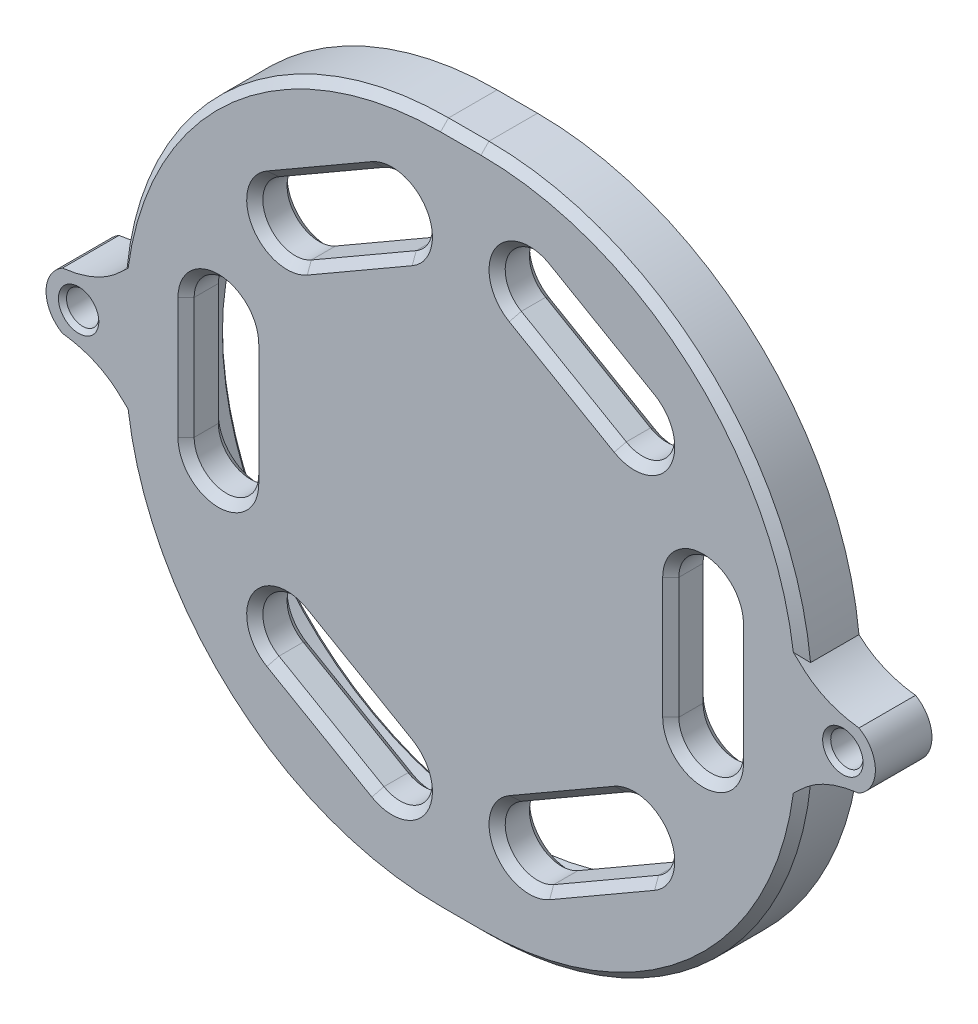
SolidWorks part; units mm, degrees
ref_plane "Plan de face" through (0, 0, 0) normal (0, 0, 1) x (1, 0, 0)
ref_plane "Plan de dessus" through (0, 0, 0) normal (0, 1, 0) x (1, 0, 0)
ref_plane "Plan de droite" through (0, 0, 0) normal (1, 0, 0) x (0, 0, -1)
sketch "Esquisse1" plane through (0, 0, 0) normal (0, 0, 1) x (1, 0, 0)
  line L1 (-2.5, -42.5) -> (2.5, -42.5)
  line L2 (-42.5, -2.5) -> (-42.5, 2.5)
  line L3 (-2.5, 42.5) -> (2.5, 42.5)
  line L4 (42.5, -2.5) -> (42.5, 2.5)
  line L5 (-42.5, -42.5) -> (42.5, 42.5) construction
  line L6 (-42.5, 42.5) -> (42.5, -42.5) construction
  arc A0 (-2.5, -42.5) -> (-42.5, -2.5) centre (-2.5, -2.5) cw
  arc A1 (2.5, 42.5) -> (42.5, 2.5) centre (2.5, 2.5) cw
  arc A2 (2.5, -42.5) -> (42.5, -2.5) centre (2.5, -2.5) ccw
  arc A3 (-42.5, 2.5) -> (-2.5, 42.5) centre (-2.5, 2.5) cw
  point P0 (0, 0)
  dimension "D3" = 40
  dimension "D1" = 85
  dimension "D2" = 85
extrude "Boss.-Extru.1" add sketch "Esquisse1" along normal blind 7
sketch "Esquisse2" plane through (0, 0, 0) normal (0, 0, -1) x (-1, 0, 0)
  circle A0 centre (0, 0) radius 36
  dimension "D1" = 72
extrude "Enlèv. mat.-Extru.1" cut sketch "Esquisse2" against normal blind 2
sketch "Esquisse3" plane through (0, 0, 0) normal (0, 0, -1) x (-1, 0, 0)
  line L0 (0, 0) -> (0, 9.4107) construction
  line L5 (-42.2995, 6.5) -> (-42.2995, -6.5)
  line L6 (-49.2995, 3.5) -> (-49.2995, -3.5) construction
  line L7 (42.2995, 6.5) -> (42.2995, -6.5)
  arc A0 (-49.2995, 3.5) -> (-49.2995, -3.5) centre (-47.2995, 0) ccw
  arc A1 (-2.5, 42.5) -> (-42.5, 2.5) centre (-2.5, 2.5) ccw construction
  arc A2 (-42.5, -2.5) -> (-2.5, -42.5) centre (-2.5, -2.5) ccw construction
  circle A3 centre (-47.2995, 0) radius 2
  circle A4 centre (47.2995, 0) radius 2
  arc A5 (49.2995, 3.5) -> (49.2995, -3.5) centre (47.2995, 0) cw
  spline S0 degree 2 poles (-49.2995, 3.5) (-45, 4) (-42.2995, 6.5) knots 0 0 0 0.627422 0.627422 0.627422
  spline S1 degree 2 poles (-49.2995, -3.5) (-45, -4) (-42.2995, -6.5) knots 0 0 0 0.742649 0.742649 0.742649
  spline S2 degree 2 poles (49.2995, 3.5) (45, 4) (42.2995, 6.5) knots 0 0 0 0.627422 0.627422 0.627422
  spline S3 degree 2 poles (49.2995, -3.5) (45, -4) (42.2995, -6.5) knots 0 0 0 0.742649 0.742649 0.742649
  dimension "D3" = 4
  dimension "D1" = 7
  dimension "D2" = 13
  dimension "D4" = 5
  dimension "D5" = 7
extrude "Boss.-Extru.2" add sketch "Esquisse3" against normal blind 7
chamfer "Chanfrein1" distance 0.5 angle 45 2 edges at (-45.2995, 0, 7) (45.2995, 0, 7)
chamfer "Chanfrein3" distance 0.5 angle 45 1 edges at (-36, 0, 0)
sketch "Esquisse4" plane through (0, 0, 7) normal (0, 0, 1) x (1, 0, 0)
  line L0 (10, 0) -> (30, 0) construction
  line L1 (30, -7.5) -> (30, 7.5)
  line L7 (30, 7.5) -> (30, -7.5) construction
  line L8 (34, 7.5) -> (34, -7.5)
  line L9 (26, 7.5) -> (26, -7.5)
  line L10 (19.4952, -18.7667) -> (6.5048, -26.2667)
  line L11 (23.4952, -25.6949) -> (10.5048, -33.1949)
  line L12 (21.4952, -22.2308) -> (8.5048, -29.7308) construction
  line L13 (-6.5048, -26.2667) -> (-19.4952, -18.7667)
  line L14 (-10.5048, -33.1949) -> (-23.4952, -25.6949)
  line L15 (-8.5048, -29.7308) -> (-21.4952, -22.2308) construction
  line L16 (-26, -7.5) -> (-26, 7.5)
  line L17 (-34, -7.5) -> (-34, 7.5)
  line L18 (-30, -7.5) -> (-30, 7.5) construction
  line L19 (-19.4952, 18.7667) -> (-6.5048, 26.2667)
  line L20 (-23.4952, 25.6949) -> (-10.5048, 33.1949)
  line L21 (-21.4952, 22.2308) -> (-8.5048, 29.7308) construction
  line L22 (6.5048, 26.2667) -> (19.4952, 18.7667)
  line L23 (10.5048, 33.1949) -> (23.4952, 25.6949)
  line L24 (8.5048, 29.7308) -> (21.4952, 22.2308) construction
  line L25 (0, 0) -> (10, 0) construction
  arc A0 (34, 7.5) -> (26, 7.5) centre (30, 7.5) ccw
  arc A1 (26, -7.5) -> (34, -7.5) centre (30, -7.5) ccw
  arc A2 (23.4952, -25.6949) -> (19.4952, -18.7667) centre (21.4952, -22.2308) ccw
  arc A3 (6.5048, -26.2667) -> (10.5048, -33.1949) centre (8.5048, -29.7308) ccw
  arc A4 (-10.5048, -33.1949) -> (-6.5048, -26.2667) centre (-8.5048, -29.7308) ccw
  arc A5 (-19.4952, -18.7667) -> (-23.4952, -25.6949) centre (-21.4952, -22.2308) ccw
  arc A6 (-34, -7.5) -> (-26, -7.5) centre (-30, -7.5) ccw
  arc A7 (-26, 7.5) -> (-34, 7.5) centre (-30, 7.5) ccw
  arc A8 (-23.4952, 25.6949) -> (-19.4952, 18.7667) centre (-21.4952, 22.2308) ccw
  arc A9 (-6.5048, 26.2667) -> (-10.5048, 33.1949) centre (-8.5048, 29.7308) ccw
  arc A10 (10.5048, 33.1949) -> (6.5048, 26.2667) centre (8.5048, 29.7308) ccw
  arc A11 (19.4952, 18.7667) -> (23.4952, 25.6949) centre (21.4952, 22.2308) ccw
  point P2 (30, 0)
  point P6 (30, 0)
  point P11 (15, -25.9808)
  point P20 (-15, -25.9808)
  point P24 (0, 0)
  point P28 (-30, 0)
  point P35 (-15, 25.9808)
  point P42 (15, 25.9808)
  point P49 (0, 0)
  dimension "D1" = 20
  dimension "D2" = 10
  dimension "D3" = 15
  dimension "D4" = 4
  dimension "D5" = 6
extrude "Enlèv. mat.-Extru.2" cut sketch "Esquisse4" against normal blind 7 contours L9 A1 L8 A0 | L11 A3 L10 A2 | L14 A5 L13 A4 | L17 A7 L16 A6 | L20 A9 L19 A8 | L23 A11 L22 A10
chamfer "Chanfrein4" distance 1 angle 45 6 edges at (-29.3328, -32.1648, 7) (0, -42.5, 7) (29.3328, -32.1648, 7) (-29.3328, 32.1648, 7) (0, 42.5, 7) (29.3328, 32.1648, 7)
chamfer "Chanfrein5" distance 1 angle 45 48 edges at (-5.0407, -31.7308, 7) (-13, -22.5167, 7) (-17, -29.4449, 7) (-24.9593, -20.2308, 7) (-5.0407, -31.7308, 2) (-17, -29.4449, 2) (-13, -22.5167, 2) (-24.9593, -20.2308, 2) (5.0407, -31.7308, 7) (17, -29.4449, 7) (13, -22.5167, 7) (24.9593, -20.2308, 7) (5.0407, -31.7308, 2) (13, -22.5167, 2) (17, -29.4449, 2) (24.9593, -20.2308, 2) (-30, -11.5, 7) (-26, 0, 7) (-34, 0, 7) (-30, 11.5, 7) (-30, -11.5, 2) (-34, 0, 2) (-26, 0, 2) (-30, 11.5, 2) (30, -11.5, 7) (34, 0, 7) (26, 0, 7) (30, 11.5, 7) (30, -11.5, 2) (26, 0, 2) (34, 0, 2) (30, 11.5, 2) (24.9593, 20.2308, 7) (17, 29.4449, 7) (13, 22.5167, 7) (5.0407, 31.7308, 7) (24.9593, 20.2308, 2) (13, 22.5167, 2) (17, 29.4449, 2) (5.0407, 31.7308, 2) (-13, 22.5167, 7) (-5.0407, 31.7308, 7) (-17, 29.4449, 7) (-24.9593, 20.2308, 7) (-13, 22.5167, 2) (-5.0407, 31.7308, 2) (-17, 29.4449, 2) (-24.9593, 20.2308, 2)
